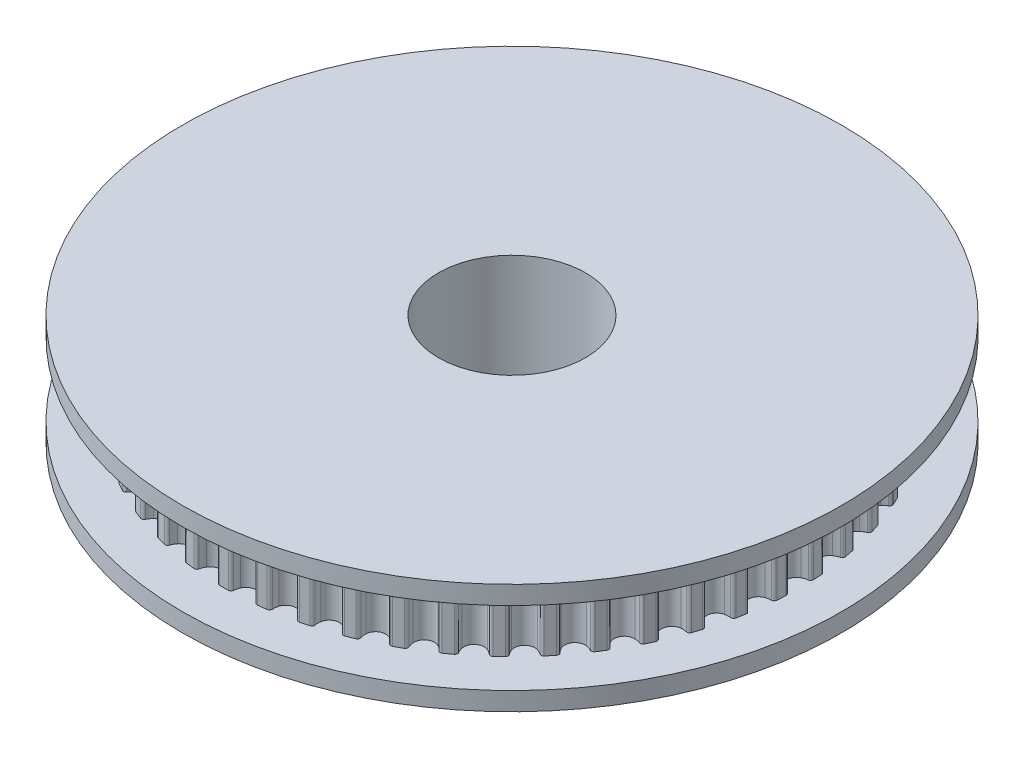
SolidWorks part; units mm, degrees
ref_plane "Front Plane" through (0, 0, 0) normal (0, 0, 1) x (1, 0, 0)
ref_plane "Top Plane" through (0, 0, 0) normal (0, 1, 0) x (1, 0, 0)
ref_plane "Right Plane" through (0, 0, 0) normal (1, 0, 0) x (0, 0, -1)
sketch "Sketch1" plane through (0, 0, 0) normal (0, 1, 0) x (1, 0, 0)
  circle A0 centre (0, 0) radius 15.9155
  dimension "D1" = 31.831
extrude "Boss-Extrude1" add sketch "Sketch1" along normal mid plane 4
sketch "Sketch2" plane through (0, 0, 0) normal (0, 1, 0) x (1, 0, 0)
  line L0 (0, 0) -> (0, 15.6615) construction
  line L1 (0, 0) -> (0.9711, 15.436) construction
  line L2 (0, 15.6615) -> (0, 15.9155)
  line L3 (0.9711, 15.436) -> (0.9993, 15.8841) construction
  line L4 (0.9993, 15.8841) -> (1.3982, 15.854) construction
  line L5 (1.3982, 15.854) -> (1.3799, 15.6119) construction
  line L6 (1.9629, 15.538) -> (1.9947, 15.79)
  arc A1 (0, 15.6615) -> (0.2367, 15.6597) centre (0, 0) cw
  arc A2 (0.2367, 15.6597) -> (0.3839, 15.523) centre (0.2345, 15.5097) cw
  arc A3 (0.3839, 15.523) -> (0.4613, 15.2166) centre (1.3799, 15.6119) ccw
  arc A4 (0.4613, 15.2166) -> (1.4494, 15.1545) centre (0.9711, 15.436) ccw
  circle A5 centre (0, 0) radius 15.9155 construction
  arc A6 (0, 15.9155) -> (1.9947, 15.79) centre (0, 0) cw
  arc A7 (1.5647, 15.4488) -> (1.4494, 15.1545) centre (0.5876, 15.6617) cw
  arc A8 (1.7278, 15.5659) -> (1.5647, 15.4488) centre (1.7113, 15.4168) ccw
  arc A9 (1.9629, 15.538) -> (1.7278, 15.5659) centre (0, 0) ccw
  dimension "D2" = 0.15
  dimension "D3" = 1
  dimension "D4" = 0.555
  dimension "D1" = 3.6
  dimension "D5" = 0.254
  dimension "D6" = 0.4
  dimension "D7" = 1.004
extrude "Cut-Extrude1" cut sketch "Sketch2" against normal through all both and the other way through all
pattern_circular "CirPattern1" count 50 over 360 about axis through (0, 2, 0) along (0, -1, 0) of "Cut-Extrude1"
sketch "Sketch3" plane through (0, 0, 0) normal (0, 1, 0) x (1, 0, 0)
  circle A0 centre (0, 0) radius 17.9155
  dimension "D1" = 35.831
extrude "Boss-Extrude2" add sketch "Sketch3" along normal blind 1 from surface starting at face at (0, 2, 0)
extrude "Boss-Extrude3" add sketch "Sketch3<2>" against normal blind 1 from surface starting at face at (0, -2, 0)
sketch "Sketch3<2>" plane through (0, 0, 0) normal (0, 1, 0) x (1, 0, 0) same geometry as "Sketch3"
sketch "Sketch4" plane through (0, 0, 0) normal (0, 1, 0) x (1, 0, 0)
  circle A0 centre (0, 0) radius 4
  dimension "D1" = 8
extrude "Cut-Extrude2" cut sketch "Sketch4" against normal through all both and the other way through all
equation "\"n\"= 50"
equation "\"p\"= 2mm"
equation "\"pd\"= ( \"n\" * \"p\" ) / pi"
equation "\"D1@Sketch1\"=\"pd\""
equation "\"D1@Sketch2\"=180/\"n\""
equation "\"D1@CirPattern1\"=\"n\""
equation "\"D1@Sketch3\"=\"pd\"+4mm"
